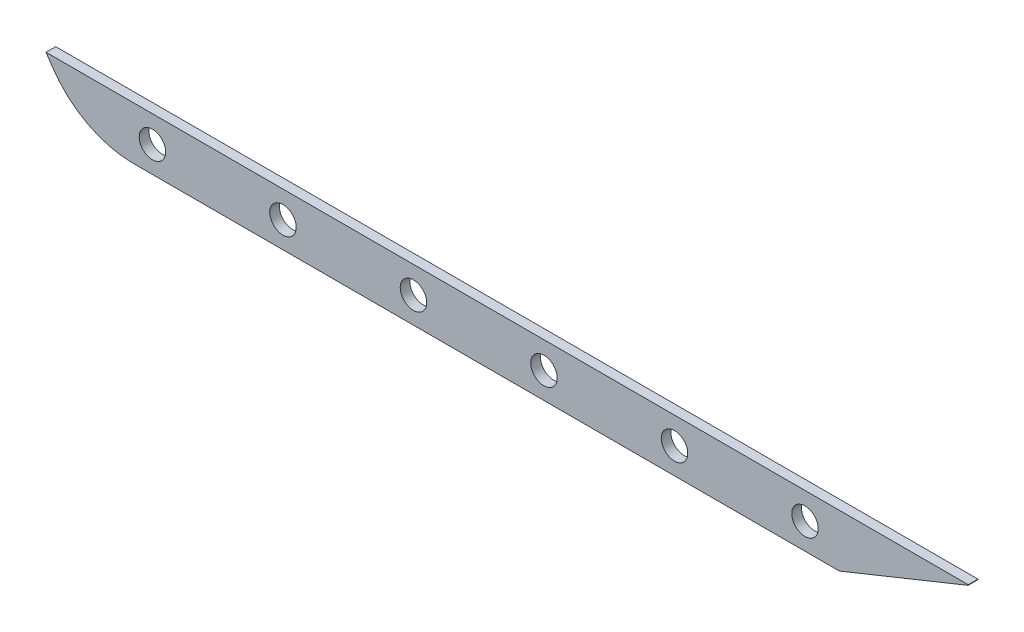
SolidWorks part; units mm, degrees
material "5052-H34"
ref_plane "Front Plane" through (0, 0, 0) normal (0, 0, 1) x (1, 0, 0)
ref_plane "Top Plane" through (0, 0, 0) normal (0, 1, 0) x (1, 0, 0)
ref_plane "Right Plane" through (0, 0, 0) normal (1, 0, 0) x (0, 0, -1)
sketch "Sketch1" plane through (0, 0, 0) normal (0, 0, 1) x (1, 0, 0)
  line L3 (428.1206, 28.9396) -> (0.5404, 28.9396)
  line L6 (-98.8794, 3.851) -> (-31.8794, -96.649)
  line L7 (428.1206, 28.9396) -> (403.1206, -71.149)
  line L9 (403.1206, -71.149) -> (366, -96.649)
  line L10 (-31.8794, -96.649) -> (366, -96.649)
  line L11 (0.5404, 28.9396) -> (-115.6052, 28.9396)
  line L12 (-98.8794, 3.851) -> (-115.6052, 28.9396)
  line L13 (-49.0861, -70.839) -> (403.198, -70.839)
  circle A0 centre (3.1206, -83.899) radius 6.5
  circle A1 centre (67.1206, -83.899) radius 6.5
  circle A2 centre (131.1206, -83.899) radius 6.5
  circle A3 centre (195.1206, -83.899) radius 6.5
  circle A4 centre (259.1206, -83.899) radius 6.5
  circle A5 centre (323.1206, -83.899) radius 6.5
  point P0 (-48.8794, -71.149)
  point P2 (-31.8794, -96.649)
  point P8 (48, -83.899)
  point P9 (403.1206, -71.149)
  point P23 (-49.0861, -70.839)
  point P25 (403.198, -70.839)
  dimension "D2" = 64
  dimension "D4" = 64
  dimension "D1" = 25.5
  dimension "D3" = 75
  dimension "D5" = 25
  dimension "D6" = 80
  dimension "D7" = 527
  dimension "D8" = 180
  dimension "D9" = 64
  dimension "D10" = 64
  dimension "D11" = 64
  dimension "D12" = 123.69
  dimension "D13" = 12.75
  dimension "D14" = 25.81
  dimension "D15" = 25.81
extrude "Boss-Extrude1" add sketch "Sketch1" along normal blind 4.7625 contours L3 L11 L12 L6 L10 L9 L7
extrude "Cut-Extrude1" cut sketch "Sketch1<4>" along normal through all contours A0 | A1 | A2 | A3 | A4 | A5 region at (3.1206, -83.899, 0)
sketch "Sketch1<4>" plane through (0, 0, 0) normal (0, 0, 1) x (1, 0, 0) same geometry as "Sketch1"
sketch "Sketch2" plane through (0, 0, 0) normal (0, 0, -1) x (-1, 0, 0)
  circle A0 centre (-291.1206, -83.899) radius 6.5
  circle A2 centre (-241.5603, -124.3932) radius 6.5
  circle A3 centre (-192, -83.899) radius 6.5
  circle A4 centre (-128, -83.899) radius 6.5
  circle A5 centre (-64, -83.899) radius 6.5
  circle A6 centre (0, -83.899) radius 6.5
  dimension "D2" = 0
  dimension "D3" = 64
  dimension "D4" = 64
  dimension "D5" = 64
  dimension "D6" = 64
  dimension "D7" = 64
  dimension "D1" = 32
sketch "Sketch5" plane through (0, 0, 0) normal (0, 0, -1) x (-1, 0, 0)
  line L0 (48.8794, -71.149) -> (-14.2353, -96.649)
  line L1 (31.8794, -96.649) -> (-366, -96.649) construction
  line L2 (-14.2353, -96.649) -> (31.8794, -96.649)
  line L3 (31.8794, -96.649) -> (48.8794, -71.149)
  line L6 (-366, -96.649) -> (-403.1206, -71.149)
  line L7 (-403.1206, -71.149) -> (-352, -71.149)
  line L9 (-352, -71.149) -> (-326.5, -96.649)
  line L11 (-366, -96.649) -> (-326.5, -96.649)
  dimension "D1" = 22
  dimension "D2" = 45
extrude "Cut-Extrude2" [suppressed] cut sketch "Sketch5" against normal up to next
sketch "Sketch6" plane through (0, 0, 4.7625) normal (0, 0, 1) x (1, 0, 0)
  line L0 (-48.8794, -71.149) -> (14.2353, -96.649)
  line L1 (-31.8794, -96.649) -> (366, -96.649) construction
  line L2 (14.2353, -96.649) -> (-31.8794, -96.649)
  line L3 (-31.8794, -96.649) -> (-48.8794, -71.149)
  dimension "D1" = 158
fillet "Fillet1" radius 48 1 edges at (-31.8794, -96.649, 2.3813)
sketch "Sketch7" plane through (0, 0, 4.7625) normal (0, 0, 1) x (1, 0, 0)
  line L0 (403.1206, -71.149) -> (340.0059, -96.649)
  line L1 (-31.8794, -96.649) -> (366, -96.649) construction
  line L2 (340.0059, -96.649) -> (366, -96.649)
  line L3 (366, -96.649) -> (403.1206, -71.149)
  dimension "D1" = 22
extrude "Cut-Extrude3" cut sketch "Sketch7" against normal blind 10
sketch "Sketch9" plane through (0, 0, 0) normal (0, 0, -1) x (-1, 0, 0)
  line L0 (-403.1206, -71.149) -> (48.8794, -71.149)
  line L1 (48.8794, -71.149) -> (48.8794, -114.9143)
  line L2 (48.8794, -114.9143) -> (-403.1206, -114.9143)
  line L3 (-403.1206, -114.9143) -> (-403.1206, -71.149)
extrude "Cut-Extrude4" [suppressed] cut sketch "Sketch9" against normal blind 10
sketch "Sketch11" plane through (0, 0, 4.7625) normal (0, 0, 1) x (1, 0, 0)
  line L0 (-49.0861, -70.839) -> (403.198, -70.839) construction
  line L1 (-49.0861, -70.839) -> (403.198, -70.839)
  line L3 (-115.6052, 28.9396) -> (428.1206, 28.9396)
  line L4 (428.1206, 28.9396) -> (403.198, -70.839)
  line L5 (-49.0861, -70.839) -> (-115.6052, 28.9396)
extrude "Cut-Extrude5" cut sketch "Sketch11" against normal blind 10
